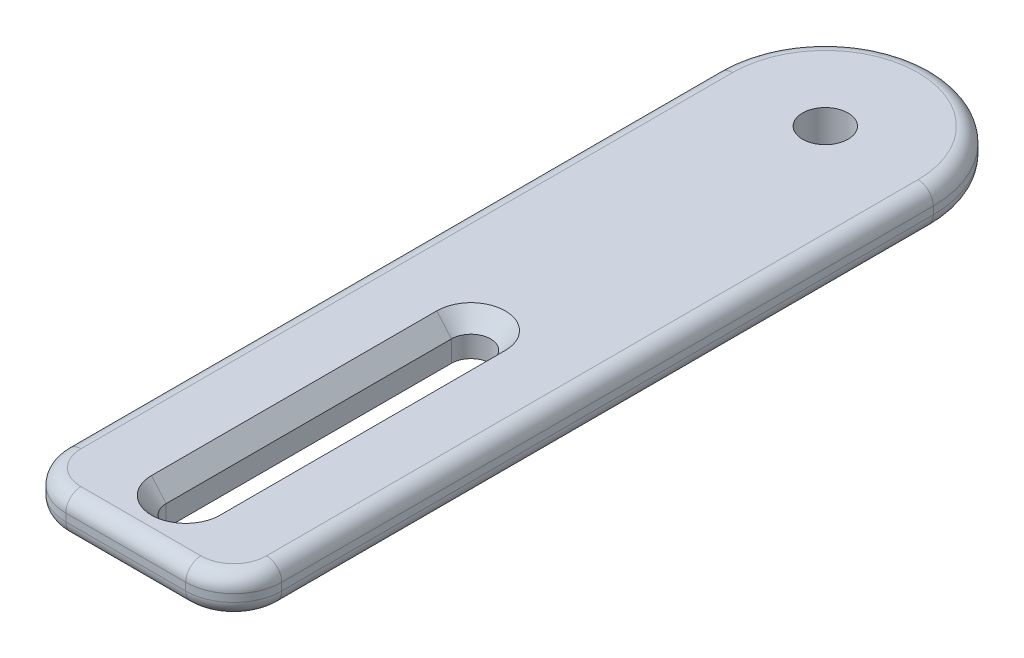
SolidWorks part; units mm, degrees
material "6061 Alloy"
ref_plane "Front Plane" through (0, 0, 0) normal (0, 0, 1) x (1, 0, 0)
ref_plane "Top Plane" through (0, 0, 0) normal (0, 1, 0) x (1, 0, 0)
ref_plane "Right Plane" through (0, 0, 0) normal (1, 0, 0) x (0, 0, -1)
sketch "Sketch1" plane through (0, 0, 0) normal (0, 1, 0) x (1, 0, 0)
  line L0 (9, 67.31) -> (9, 0) construction
  line L9 (0, 58.31) -> (0, 4)
  line L10 (4, 0) -> (14, 0)
  line L11 (18, 58.31) -> (18, 4)
  line L12 (6.1425, 28.78) -> (6.1425, 5)
  line L13 (7.368, 28.78) -> (7.3681, 5)
  line L14 (11.8575, 28.78) -> (11.8575, 5)
  line L15 (10.632, 28.78) -> (10.632, 5)
  arc A0 (10.632, 28.78) -> (7.368, 28.78) centre (9, 28.78) ccw
  arc A1 (7.3681, 5) -> (10.632, 5) centre (9, 5) ccw
  arc A2 (6.1425, 5) -> (11.8575, 5) centre (9, 5) ccw
  arc A3 (11.8575, 28.78) -> (6.1425, 28.78) centre (9, 28.78) ccw
  arc A4 (18, 58.31) -> (0, 58.31) centre (9, 58.31) ccw
  arc A5 (0, 4) -> (4, 0) centre (4, 4) ccw
  arc A6 (14, 0) -> (18, 4) centre (14, 4) ccw
  dimension "D5" = 3.2639
  dimension "D6" = 5.715
  dimension "D9" = 18
  dimension "D11" = 4
  dimension "D2" = 18
  dimension "D7" = 5
  dimension "D8" = 23.78
  dimension "D10" = 67.31
extrude "Link Base" add sketch "Sketch1" against normal blind 3.175 contours A4 L0 A3 L14 A2 L10 A6 L11 | L0 A4 L9 A5 L10 A2 L12 A3 | L0 A3 L12 A2 A1 L13 A0 | A3 L0 A0 L15 A1 A2 L14 region at (13.8871, 0, -35.473) region at (4.1129, 0, -35.473) region at (11.0663, 0, -16.89) region at (6.9337, 0, -16.89)
extrude "Contour for Flathead Screws" cut sketch "Sketch1<3>" against normal blind 10 draft 41 contours L14 A2 L12 A3
sketch "Sketch1<3>" plane through (0, 0, 0) normal (0, 1, 0) x (1, 0, 0) same geometry as "Sketch1"
hole_wizard "#6 Clearance Hole1" positions "Sketch3" profile "Sketch2" hole size "#6" standard "Ansi Inch" end condition through all
sketch "Sketch3" plane through (0, 0, 0) normal (0, 1, 0) x (-1, 0, 0)
  line L0 (-9, -67.31) -> (-9, -58.31) construction
  arc A0 (-18, -58.31) -> (0, -58.31) centre (-9, -58.31) ccw construction
  point P0 (-9, -58.31)
sketch "Sketch2" plane through (9, 0, -58.31) normal (1, 0, 0) x (0, 0, 1)
  line L0 (0, 0) -> (0, 3.175)
  line L1 (0, 3.175) -> (1.8986, 3.175)
  line L2 (1.8986, 3.175) -> (1.8986, 0)
  line L5 (1.8986, 0) -> (0, 0)
  line L11 (0, -6.35) -> (0, 107.95) construction
  dimension "Thru Hole Dia." = 3.7973
  dimension "Thru Hole Depth" = 3.175
fillet "Fillet1" radius 1.27 12 edges at (9, -3.175, -67.31) (0, -3.175, -31.155) (1.1716, -3.175, -1.1716) (9, -3.175, 0) (16.8284, -3.175, -1.1716) (9, 0, -67.31) (0, 0, -31.155) (1.1716, 0, -1.1716) (9, 0, 0) (16.8284, 0, -1.1716) (18, -3.175, -31.155) (18, 0, -31.155)
